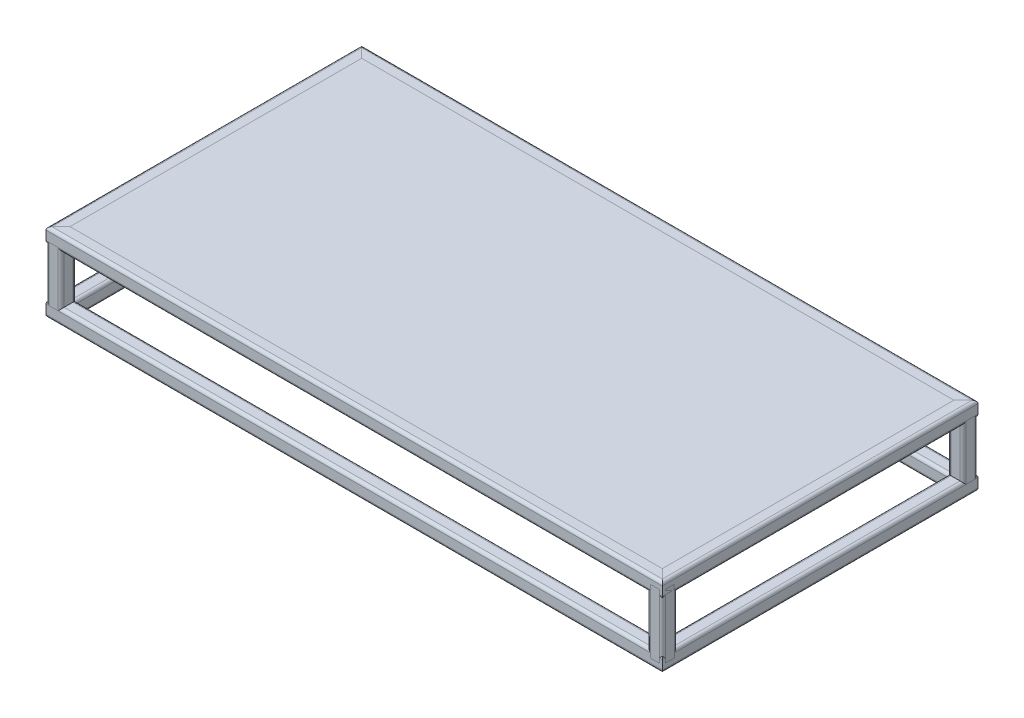
SolidWorks part; units mm, degrees
ref_plane "Front Plane" through (0, 0, 0) normal (0, 0, 1) x (1, 0, 0)
ref_plane "Top Plane" through (0, 0, 0) normal (0, 1, 0) x (1, 0, 0)
ref_plane "Right Plane" through (0, 0, 0) normal (1, 0, 0) x (0, 0, -1)
sketch3d "3DSketch1"
  line L0 (0, 0, 0) -> (0, 85, 0)
  line L1 (0, 85, 0) -> (0, 85, -400)
  line L2 (0, 85, -400) -> (0, 0, -400)
  line L3 (0, 85, 0) -> (800, 85, 0)
  line L4 (0, 85, -400) -> (800, 85, -400)
  line L5 (800, 85, 0) -> (800, 0, 0)
  line L6 (800, 85, -400) -> (800, 0, -400)
  line L7 (800, 85, 0) -> (800, 85, -400)
  line L8 (0, 0, 0) -> (800, 0, 0)
  line L9 (800, 0, 0) -> (800, 0, -400)
  line L10 (0, 0, -400) -> (0, 0, 0)
  line L11 (0, 0, -400) -> (800, 0, -400)
  dimension "D1" = 85
  dimension "D2" = 400
  dimension "D3" = 800
other "Square tube 20 X 20 X 2(1)" corner treatment miter
ref_plane "Plane1" through (0, 85, 0) normal (1, 0, 0) x (0, 0, -1)
sketch "Sketch11" plane through (0, 85, 0) normal (1, 0, 0) x (0, 0, -1)
  line L0 (-6, -8) -> (6, -8)
  line L1 (-8, -6) -> (-8, 6)
  line L2 (6, 8) -> (-6, 8)
  line L3 (8, 6) -> (8, -6)
  line L4 (-6, -10) -> (6, -10)
  line L5 (-10, -6) -> (-10, 6)
  line L6 (6, 10) -> (-6, 10)
  line L7 (10, 6) -> (10, -6)
  arc A0 (10, 6) -> (6, 10) centre (6, 6) ccw
  arc A1 (6, -10) -> (10, -6) centre (6, -6) ccw
  arc A2 (-10, -6) -> (-6, -10) centre (-6, -6) ccw
  arc A3 (-6, 10) -> (-10, 6) centre (-6, 6) ccw
  arc A4 (-6, 8) -> (-8, 6) centre (-6, 6) ccw
  arc A5 (8, 6) -> (6, 8) centre (6, 6) ccw
  arc A6 (6, -8) -> (8, -6) centre (6, -6) ccw
  arc A7 (-8, -6) -> (-6, -8) centre (-6, -6) ccw
  point P0 (-10, 0)
  point P1 (10, 0)
  point P2 (0, 10)
  point P3 (0, -10)
  point P4 (0, 0)
  point P5 (-10, -10)
  point P6 (10, -10)
  point P7 (10, 10)
  point P8 (-10, 10)
  point P33 (0, 0)
  dimension "D1" = 4
  dimension "Thickness" = 2
  dimension "V_leg" = 20
other "Square tube 20 X 20 X 2(2)" corner treatment miter
ref_plane "Plane2" through (0, 0, 0) normal (0, 1, 0) x (1, 0, 0)
sketch "Sketch1" plane through (0, 0, 0) normal (0, 1, 0) x (1, 0, 0)
  line L0 (-6, -8) -> (6, -8)
  line L1 (-8, -6) -> (-8, 6)
  line L2 (6, 8) -> (-6, 8)
  line L3 (8, 6) -> (8, -6)
  line L4 (-6, -10) -> (6, -10)
  line L5 (-10, -6) -> (-10, 6)
  line L6 (6, 10) -> (-6, 10)
  line L7 (10, 6) -> (10, -6)
  arc A0 (10, 6) -> (6, 10) centre (6, 6) ccw
  arc A1 (6, -10) -> (10, -6) centre (6, -6) ccw
  arc A2 (-10, -6) -> (-6, -10) centre (-6, -6) ccw
  arc A3 (-6, 10) -> (-10, 6) centre (-6, 6) ccw
  arc A4 (-6, 8) -> (-8, 6) centre (-6, 6) ccw
  arc A5 (8, 6) -> (6, 8) centre (6, 6) ccw
  arc A6 (6, -8) -> (8, -6) centre (6, -6) ccw
  arc A7 (-8, -6) -> (-6, -8) centre (-6, -6) ccw
  point P0 (-10, 0)
  point P1 (10, 0)
  point P2 (0, 10)
  point P3 (0, -10)
  point P4 (0, 0)
  point P5 (-10, -10)
  point P6 (10, -10)
  point P7 (10, 10)
  point P8 (-10, 10)
  point P33 (0, 0)
  dimension "D1" = 4
  dimension "Thickness" = 2
  dimension "V_leg" = 20
sketch "Sketch12" plane through (0, 95, 0) normal (0, 1, 0) x (1, 0, 0)
  line L0 (6, 394) -> (794, 394)
  line L1 (794, 394) -> (794, 6)
  line L2 (794, 6) -> (6, 6)
  line L3 (6, 394) -> (6, 6)
base flange "Base-Flange1" sketch "Sketch12" thickness 2 reverse thickness direction no parameters "D1"=0.7366
other "Square tube 20 X 20 X 2(3)" corner treatment miter
ref_plane "Plane3" through (0, 0, -400) normal (0, 0, 1) x (1, 0, 0)
sketch "Sketch13" plane through (0, 0, -400) normal (0, 0, 1) x (1, 0, 0)
  line L0 (-6, -8) -> (6, -8)
  line L1 (-8, -6) -> (-8, 6)
  line L2 (6, 8) -> (-6, 8)
  line L3 (8, 6) -> (8, -6)
  line L4 (-6, -10) -> (6, -10)
  line L5 (-10, -6) -> (-10, 6)
  line L6 (6, 10) -> (-6, 10)
  line L7 (10, 6) -> (10, -6)
  arc A0 (10, 6) -> (6, 10) centre (6, 6) ccw
  arc A1 (6, -10) -> (10, -6) centre (6, -6) ccw
  arc A2 (-10, -6) -> (-6, -10) centre (-6, -6) ccw
  arc A3 (-6, 10) -> (-10, 6) centre (-6, 6) ccw
  arc A4 (-6, 8) -> (-8, 6) centre (-6, 6) ccw
  arc A5 (8, 6) -> (6, 8) centre (6, 6) ccw
  arc A6 (6, -8) -> (8, -6) centre (6, -6) ccw
  arc A7 (-8, -6) -> (-6, -8) centre (-6, -6) ccw
  point P0 (-10, 0)
  point P1 (10, 0)
  point P2 (0, 10)
  point P3 (0, -10)
  point P4 (0, 0)
  point P5 (-10, -10)
  point P6 (10, -10)
  point P7 (10, 10)
  point P8 (-10, 10)
  point P33 (0, 0)
  dimension "D1" = 4
  dimension "Thickness" = 2
  dimension "V_leg" = 20
sketch "Bend-Lines1" [suppressed] plane through (0, 0, 0) normal (0, 1, 0) x (1, 0, 0)
sketch "Bounding-Box1" [suppressed] plane through (0, 0, 0) normal (0, 1, 0) x (1, 0, 0)
sheet metal parameters "Sheet-Metal9" thickness 2 parameters "D1"=0.7366
flat pattern "Flat-Pattern9" [suppressed]
sketch "Bend-Lines2" plane through (0, 0, 0) normal (0, 1, 0) x (1, 0, 0)
sketch3d "Bounding-Box2" [suppressed]
  line L0 (794, 394, 0) -> (6, 394, 0) construction
  line L1 (794, 6, 0) -> (6, 6, 0) construction
  line L2 (794, 394, 0) -> (794, 6, 0) construction
  line L3 (6, 394, 0) -> (6, 6, 0) construction
